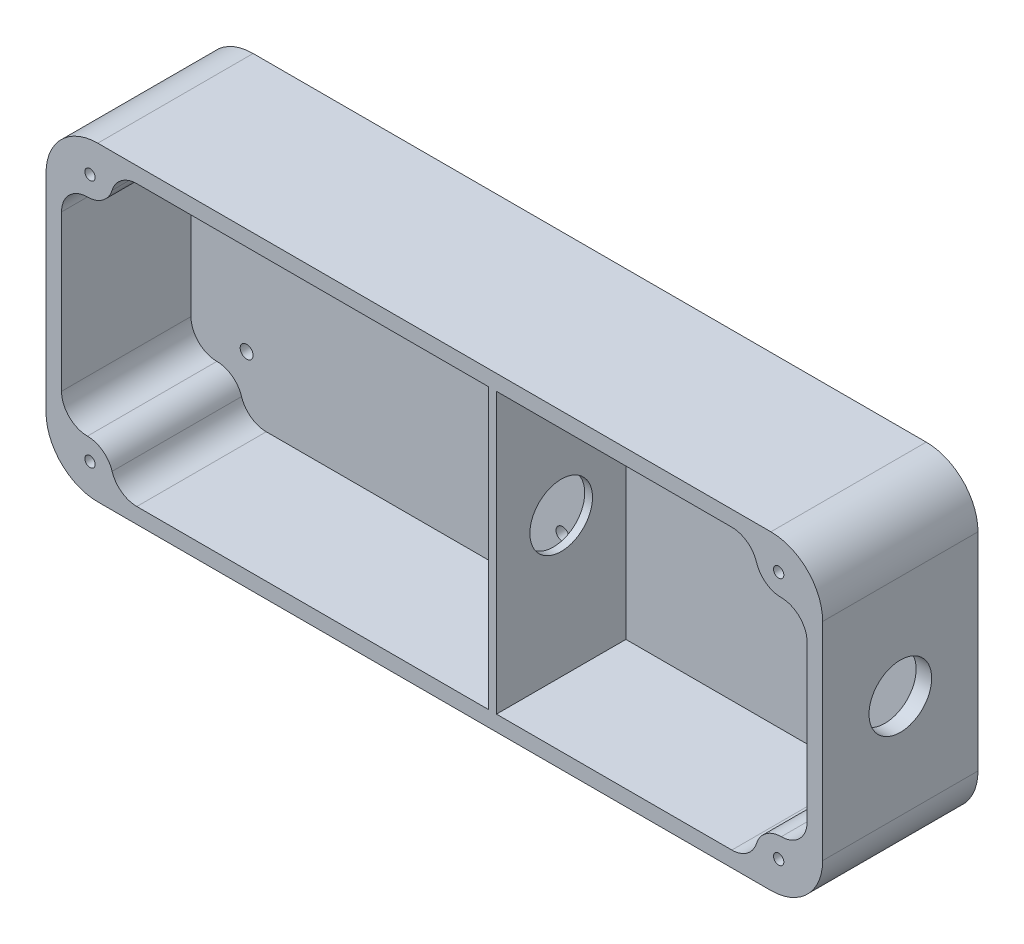
SolidWorks part; units mm, degrees
note: The reader was unsure of these and kept them because the rebuilt part matched: shared geometry of "Эскиз2<5>", "Эскиз2<7>".
ref_plane "Спереди" through (0, 0, 0) normal (0, 0, 1) x (1, 0, 0)
ref_plane "Сверху" through (0, 0, 0) normal (0, 1, 0) x (1, 0, 0)
ref_plane "Справа" through (0, 0, 0) normal (1, 0, 0) x (0, 0, -1)
sketch "Эскиз1" plane through (0, 0, 0) normal (0, 0, 1) x (1, 0, 0)
  line L13 (150, 60) -> (-150, 60)
  line L14 (150, 60) -> (150, -60)
  line L15 (150, -60) -> (-150, -60)
  line L16 (-150, 60) -> (-150, -60)
  line L17 (150, 60) -> (-150, -60) construction
  line L18 (150, -60) -> (-150, 60) construction
  point P0 (0, 0)
  dimension "D1" = 300
  dimension "D2" = 120
extrude "Бобышка-Вытянуть2" add sketch "Эскиз1" along normal blind 60 contours L14 L13 L16 L15
sketch "Эскиз2" plane through (0, 0, 60) normal (0, 0, 1) x (1, 0, 0)
  line L0 (24, -40) -> (24, 40)
  line L6 (124, -54) -> (24, -54)
  line L7 (21, -40) -> (21, 40)
  line L9 (144, -40) -> (144, 40)
  line L10 (144, 40) -> (24, 40)
  line L11 (21, -40) -> (-144, -40)
  line L12 (-144, -40) -> (-144, 40)
  line L13 (-144, 40) -> (21, 40)
  line L14 (150, 60) -> (150, -60) construction
  line L15 (150, -60) -> (-150, -60) construction
  line L16 (150, 60) -> (-150, 60) construction
  line L17 (-150, 60) -> (-150, -60) construction
  line L18 (144, -40) -> (24, -40)
  line L19 (24, 40) -> (144, 40)
  line L20 (124, -54) -> (124, -40)
  line L21 (124, -40) -> (24, -40)
  line L22 (24, -54) -> (24, -40)
  line L23 (21, -54) -> (-124, -54)
  line L24 (21, -54) -> (21, -40)
  line L25 (21, -40) -> (-124, -40)
  line L26 (-124, -54) -> (-124, -40)
  line L27 (24, 40) -> (124, 40)
  line L28 (24, 40) -> (24, 54)
  line L29 (24, 54) -> (124, 54)
  line L30 (124, 40) -> (124, 54)
  line L31 (21, 40) -> (-124, 40)
  line L32 (21, 40) -> (21, 54)
  line L33 (21, 54) -> (-124, 54)
  line L34 (-124, 40) -> (-124, 54)
  circle A0 centre (133, -48) radius 2
  circle A2 centre (133, 48) radius 2
  circle A3 centre (-133, 48) radius 2
  circle A5 centre (-133, -48) radius 2
  point P0 (0, 0)
  dimension "D15" = 4
  dimension "D16" = 4
  dimension "D17" = 4
  dimension "D18" = 4
  dimension "D21" = 6
  dimension "D2" = 80
  dimension "D3" = 120
  dimension "D4" = 3
  dimension "D5" = 165
  dimension "D6" = 80
  dimension "D7" = 17
  dimension "D8" = 12
  dimension "D9" = 17
  dimension "D10" = 12
  dimension "D11" = 12
  dimension "D12" = 17
  dimension "D13" = 17
  dimension "D14" = 12
  dimension "D19" = 6
  dimension "D20" = 20
  dimension "D22" = 9
  dimension "D23" = 6
  dimension "D24" = 9
  dimension "D25" = 6
  dimension "D26" = 9
  dimension "D27" = 6
  dimension "D28" = 9
extrude "Вырез-Вытянуть1" cut sketch "Эскиз2" against normal blind 50 contours L9 L10 L0 L18 | L13 L7 L11 L12
fillet "Скругление5" radius 20 4 edges at (150, -60, 30) (150, 60, 30) (-150, 60, 30) (-150, -60, 30)
sketch "Эскиз10" plane through (150, 0, 0) normal (1, 0, 0) x (0, 0, -1)
  line L0 (-60, -40) -> (0, 40)
  line L1 (-60, 40) -> (0, -40)
  circle A0 centre (-30, 0) radius 12.1
  dimension "D1" = 24.2
extrude "Вырез-Вытянуть5" cut sketch "Эскиз2<5>" against normal blind 40 contours A2 | A0 | A3 | A5
sketch "Эскиз2<5>" plane through (0, 0, 60) normal (0, 0, 1) x (1, 0, 0) same geometry as "Эскиз2"
extrude "Вырез-Вытянуть4" cut sketch "Эскиз10" against normal up to next contours A0
sketch "Эскиз13" plane through (0, 0, 0) normal (0, 0, -1) x (-1, 0, 0)
  line L0 (-130, 60) -> (130, 60) construction
  line L1 (-150, 40) -> (-150, -40) construction
  line L2 (-130, -60) -> (130, -60) construction
  line L3 (150, 40) -> (150, -40) construction
  circle A0 centre (-133, 48) radius 5
  circle A1 centre (-133, -48) radius 5
  circle A2 centre (133, -48) radius 5
  circle A3 centre (133, 48) radius 5
  dimension "D1" = 10
  dimension "D2" = 10
  dimension "D3" = 10
  dimension "D4" = 10
  dimension "D5" = 12
  dimension "D6" = 17
  dimension "D7" = 17
  dimension "D8" = 12
  dimension "D9" = 12
  dimension "D10" = 17
  dimension "D11" = 17
  dimension "D12" = 12
extrude "Вырез-Вытянуть7" cut sketch "Эскиз13" against normal blind 20 contours A0 | A1 | A2 | A3
sketch "Эскиз14" plane through (24, 0, 0) normal (1, 0, 0) x (0, 0, -1)
  line L0 (-60, 40) -> (-10, -40)
  line L1 (-60, -40) -> (-10, 40)
  circle A0 centre (-35, 0) radius 12.1
  dimension "D1" = 24.2
extrude "Вырез-Вытянуть8" cut sketch "Эскиз14" against normal up to next contours L0 A0 L1 | L0 A0 L1 | L1 A0 L0 | L1 A0 L0
sketch "Эскиз16" plane through (0, 0, 10) normal (0, 0, 1) x (1, 0, 0)
  line L0 (21, -40) -> (21, 40) construction
  line L1 (21, -40) -> (-144, -40) construction
  line L2 (-144, -40) -> (-144, 40) construction
  line L3 (-144, 40) -> (21, 40) construction
  circle A0 centre (-0.5, -31) radius 2.5
  circle A1 centre (-122.5, -31) radius 2.5
  circle A2 centre (-0.5, 31) radius 2.5
  circle A3 centre (-122.5, 31) radius 2.5
  dimension "D1" = 5
  dimension "D2" = 5
  dimension "D3" = 5
  dimension "D4" = 5
  dimension "D5" = 21.5
  dimension "D6" = 9
  dimension "D7" = 9
  dimension "D8" = 21.5
  dimension "D9" = 21.5
  dimension "D10" = 9
  dimension "D11" = 9
  dimension "D12" = 21.5
extrude "Вырез-Вытянуть9" cut sketch "Эскиз16" against normal blind 6 contours A0 | A1 | A3 | A2
extrude "Вырез-Вытянуть10" cut sketch "Эскиз2<7>" against normal blind 50 contours L22 L6 L20 L18 | L26 L23 L24 L11 | L34 L13 L32 L33 | L19 L30 L29 L28
sketch "Эскиз2<7>" plane through (0, 0, 60) normal (0, 0, 1) x (1, 0, 0) same geometry as "Эскиз2"
fillet "Скругление6" radius 10 1 edges at (-124, -40, 35)
fillet "Скругление7" radius 10 1 edges at (-144, -40, 35)
fillet "Скругление8" radius 10 1 edges at (124, -40, 35)
fillet "Скругление9" radius 10 1 edges at (144, -40, 35)
fillet "Скругление10" radius 10 1 edges at (124, 40, 35)
fillet "Скругление11" radius 10 1 edges at (124, -54, 35)
fillet "Скругление12" radius 10 1 edges at (-124, -54, 35)
fillet "Скругление14" radius 10 2 edges at (-144, 40, 35) (-124, 40, 35)
fillet "Скругление15" radius 10 1 edges at (-124, 54, 35)
fillet "Скругление16" radius 10 2 edges at (124, 54, 35) (144, 40, 35)
